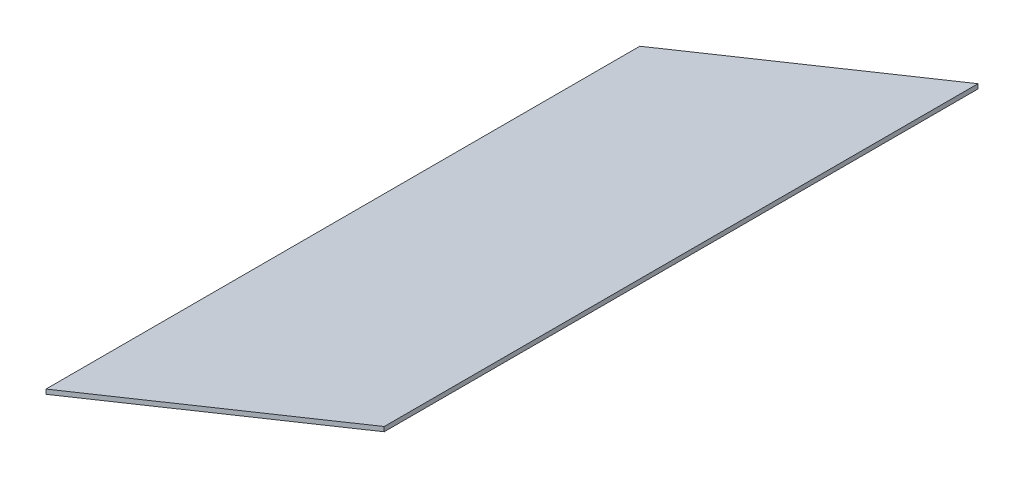
SolidWorks part; units mm, degrees
ref_plane "Front Plane" through (0, 0, 0) normal (0, 0, 1) x (1, 0, 0)
ref_plane "Top Plane" through (0, 0, 0) normal (0, 1, 0) x (1, 0, 0)
ref_plane "Right Plane" through (0, 0, 0) normal (1, 0, 0) x (0, 0, -1)
sketch "Sketch1" plane through (0, 0, 0) normal (0, 0, 1) x (1, 0, 0)
  line L0 (0, 0) -> (398.6891, 161.0808)
  line L1 (0, 0) -> (0, -5)
  line L2 (1.873, -4.6359) -> (398.6891, 155.6882)
  line L3 (398.6891, 161.0808) -> (398.6891, 155.6882)
  line L4 (1.873, -4.6359) -> (0, -5.3927)
  line L5 (0, -5) -> (0, -5.3927)
  line L6 (1.873, -4.6359) -> (400.5621, 156.4449) construction
  line L7 (0, -5.3927) -> (115.4899, -5.3927) construction
  dimension "D1" = 430
  dimension "D2" = 5
  dimension "D3" = 22
extrude "Boss-Extrude1" add sketch "Sketch1" along normal blind 350 and the other way blind 350
